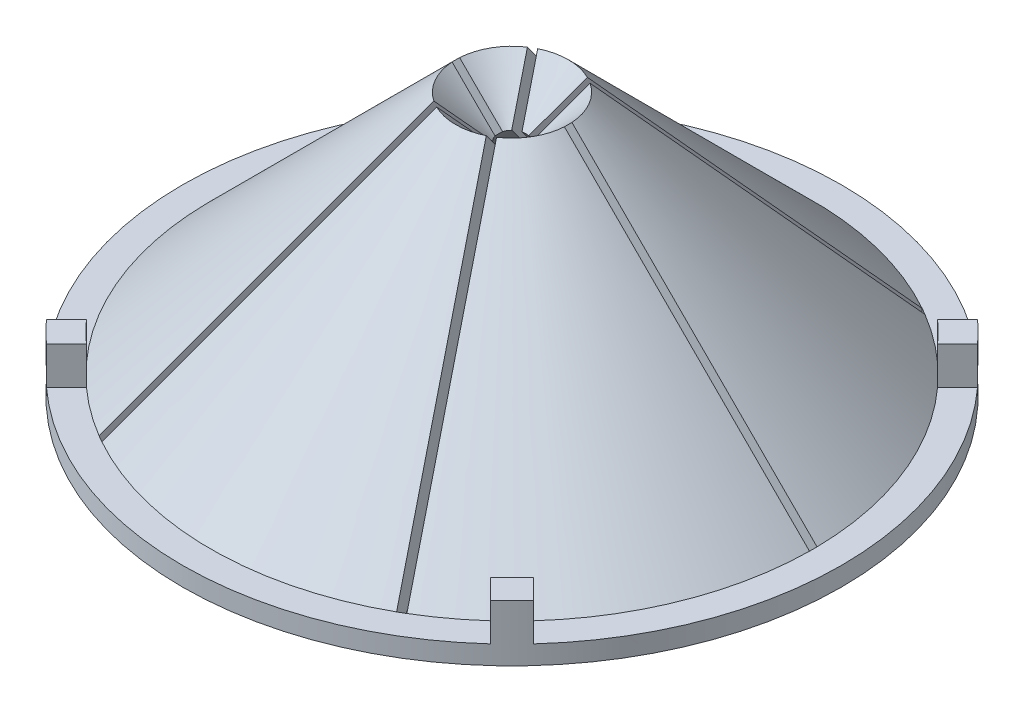
SolidWorks part; units mm, degrees
material "合金钢"
ref_plane "前视基准面" through (0, 0, 0) normal (0, 0, 1) x (1, 0, 0)
ref_plane "上视基准面" through (0, 0, 0) normal (0, 1, 0) x (1, 0, 0)
ref_plane "右视基准面" through (0, 0, 0) normal (1, 0, 0) x (0, 0, -1)
other "Configuration Table"
sketch "草图1" plane through (0, 0, 0) normal (0, 0, 1) x (1, 0, 0)
  line L0 (0, 35.7861) -> (0, -42.9253) construction
  line L1 (-0.9289, 7.0711) -> (-8, 0) construction
  line L2 (-1.4946, 7.6368) -> (-8, 1.1314)
  line L3 (-0.3632, 6.5054) -> (-6.2373, 0.6314)
  line L4 (-1.4946, 7.6368) -> (-0.3632, 6.5054)
  line L6 (-0.3632, 6.5054) -> (-7.6136, -0.7449) construction
  line L7 (-1.4946, 7.6368) -> (-8.7449, 0.3864) construction
  line L8 (-0.9289, 7.0711) -> (-8.1793, -0.1793) construction
  line L9 (0, 0) -> (-12.8023, 0) construction
  line L10 (-6.2373, 0.6314) -> (-8.75, 0.6314)
  line L11 (-8.75, 0.6314) -> (-8.75, 1.1314)
  line L12 (-8.75, 1.1314) -> (-8, 1.1314)
  point P10 (-6.5931, 0.2755)
  dimension "D1" = 45
  dimension "D4" = 10
  dimension "D5" = 8
  dimension "D6" = 17.5
  dimension "D7" = 0.5
  dimension "D2" = 0.8
  dimension "D3" = 0.8
revolve "旋转2" add sketch "草图1" angle 360 about L0
sketch "草图2" plane through (0, 0, 0) normal (0, 1, 0) x (1, 0, 0)
  line L0 (0, 0) -> (11.8353, 0) construction
  line L1 (0, -0.1) -> (7.9994, -0.1)
  line L2 (0, 0.1) -> (7.9994, 0.1)
  line L3 (0, 0.1) -> (11.8353, 0.1) construction
  line L4 (0, -0.1) -> (11.8353, -0.1) construction
  line L5 (0, 0.1) -> (0, -0.1)
  circle A0 centre (0, 0) radius 8 construction
  arc A1 (7.9994, -0.1) -> (7.9994, 0.1) centre (0, 0) ccw
  dimension "D1" = 0.1
  dimension "D2" = 0.1
extrude "切除-拉伸1" cut sketch "草图2" along normal up to next and the other way blind 10
pattern_circular "阵列(圆周)1" count 6 over 360 about axis through (0, 1.1314, 0) along (0, 1, 0) of "切除-拉伸1"
sketch "草图3" plane through (0, 1.1314, 0) normal (0, 1, 0) x (1, 0, 0)
  line L0 (-10.3064, 0) -> (11.4036, 0) construction
  line L1 (0, 9.2722) -> (0, -9.506) construction
  line L2 (0, 0) -> (-8.1209, 8.1209) construction
  line L7 (-5.3669, 5.9326) -> (-5.8979, 6.4636)
  line L8 (-5.9326, 5.3669) -> (-6.4636, 5.8979)
  arc A2 (-4.0863, 6.8777) -> (-7.9994, 0.1) centre (0, 0) ccw construction
  arc A3 (-5.3669, 5.9326) -> (-5.9326, 5.3669) centre (0, 0) ccw
  arc A4 (-5.8979, 6.4636) -> (-6.4636, 5.8979) centre (0, 0) ccw
  circle A5 centre (0, 0) radius 8.75 construction
  dimension "D2" = 0.8
  dimension "D1" = 45
extrude "凸台-拉伸1" add sketch "草图3" along normal blind 1
pattern_circular "阵列(圆周)2" count 4 over 360 about axis through (0, 1.1314, 0) along (0, 1, 0) of "凸台-拉伸1"
